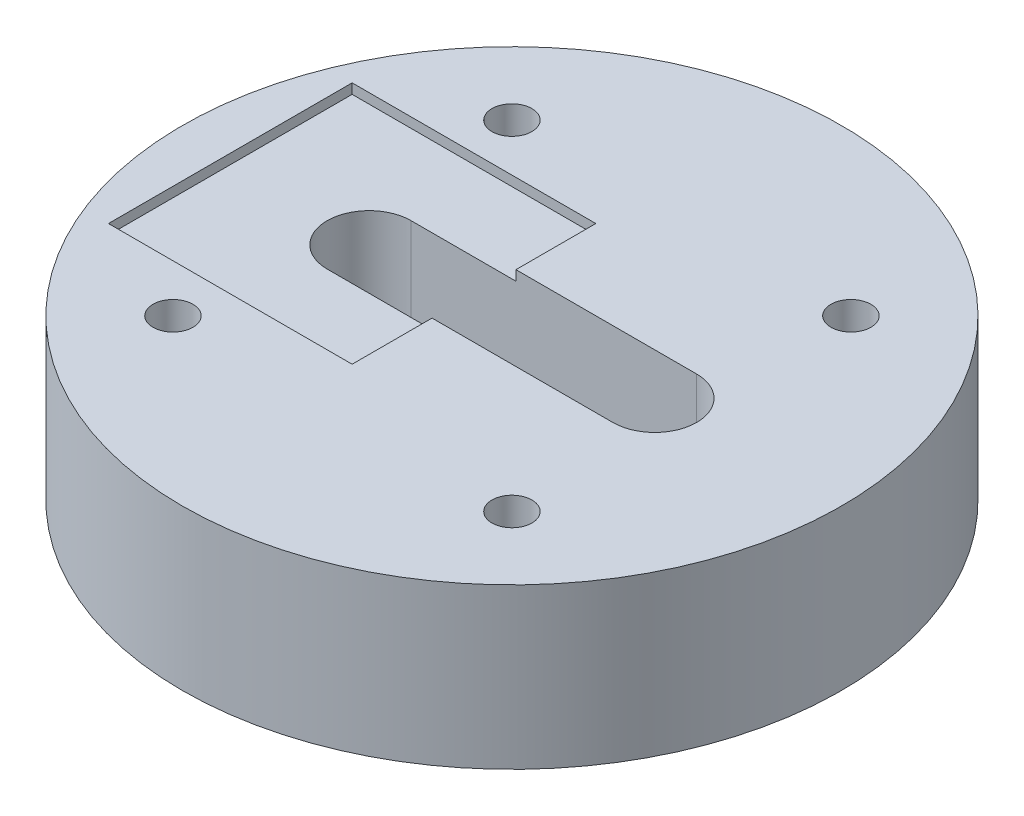
SolidWorks part; units mm, degrees
ref_plane "前视基准面" through (0, 0, 0) normal (0, 0, 1) x (1, 0, 0)
ref_plane "上视基准面" through (0, 0, 0) normal (0, 1, 0) x (1, 0, 0)
ref_plane "右视基准面" through (0, 0, 0) normal (1, 0, 0) x (0, 0, -1)
other "Configuration Table"
sketch "草图1" plane through (0, 0, 0) normal (0, 1, 0) x (1, 0, 0)
  circle A0 centre (0, 0) radius 16.5
  circle A1 centre (0, 0) radius 15.5
  dimension "D1" = 33
  dimension "D2" = 31
extrude "凸台-拉伸1" add sketch "草图1" along normal blind 8 contours A0
extrude "凸台-拉伸2" add sketch "草图1<5>" along normal blind 6 contours A0 | A1
sketch "草图1<5>" plane through (0, 0, 0) normal (0, 1, 0) x (1, 0, 0) same geometry as "草图1"
sketch "草图2" plane through (0, 8, 0) normal (0, 1, 0) x (1, 0, 0)
  line L1 (4.25, 2.1) -> (-4.25, 2.1)
  line L2 (4.25, 2.1) -> (4.25, -2.1)
  line L3 (4.25, -2.1) -> (-4.25, -2.1)
  line L4 (-4.25, 2.1) -> (-4.25, -2.1)
  line L5 (4.25, 2.1) -> (-4.25, -2.1) construction
  line L6 (4.25, -2.1) -> (-4.25, 2.1) construction
  circle A0 centre (4.25, 0) radius 2.1
  circle A1 centre (-4.25, 0) radius 2.1
  dimension "D1" = 4.2
  dimension "D2" = 8.5
extrude "切除-拉伸1" cut sketch "草图2" against normal through all contours L4 A1 | L2 A0 | L1 L4 L3 L2 region at (5.1413, 8, 0) region at (-5.1413, 8, 0)
sketch "草图3" plane through (0, 8, 0) normal (0, 1, 0) x (1, 0, 0)
  line L1 (-7.15, -2.1) -> (7.15, -2.1)
  line L2 (-7.15, -2.1) -> (-7.15, 2.1)
  line L3 (-7.15, 2.1) -> (7.15, 2.1)
  line L4 (7.15, -2.1) -> (7.15, 2.1)
  line L5 (-7.15, -2.1) -> (7.15, 2.1) construction
  line L6 (-7.15, 2.1) -> (7.15, -2.1) construction
  circle A0 centre (-7.15, 0) radius 2.1
  circle A1 centre (7.15, 0) radius 2.1
  point P0 (0, 0)
  dimension "D1" = 4.2
  dimension "D2" = 14.3
extrude "切除-拉伸2" cut sketch "草图3" against normal offset from surface (6 mm away) 2 contours L2 A0 | L4 A1 | L3 L4 L1 L2 region at (-8.0413, 8, 0) region at (8.0413, 8, 0) up to face at (0, 0, 16.5)
sketch "草图4" plane through (0, 2, 0) normal (0, 1, 0) x (1, 0, 0)
  circle A0 centre (-7.7, 0) radius 0.4
  circle A1 centre (7.7, 0) radius 0.4
  dimension "D1" = 0.8
extrude "切除-拉伸3" cut sketch "草图4" against normal blind 2
sketch "草图5" plane through (0, 8, 0) normal (0, 1, 0) x (1, 0, 0)
  line L0 (5.1, 0) -> (0, 0) construction
  line L1 (-1.9, 6.1) -> (-14.1, 6.1)
  line L2 (-1.9, 6.1) -> (-1.9, -6.1)
  line L3 (-1.9, -6.1) -> (-14.1, -6.1)
  line L4 (-14.1, 6.1) -> (-14.1, -6.1)
  line L5 (5.1, 1.6) -> (-1.9, 1.6)
  line L6 (5.1, 1.6) -> (5.1, -1.6)
  line L7 (5.1, -1.6) -> (-1.9, -1.6)
  line L8 (-1.9, 1.6) -> (-1.9, -1.6)
  line L9 (0, 0) -> (-8, 0) construction
  line L10 (-8, 6.1) -> (-8, -6.1) construction
  dimension "D1" = 12.2
  dimension "D2" = 7
  dimension "D3" = 3.2
  dimension "D4" = 8
extrude "切除-拉伸4" cut sketch "草图5" against normal blind 0.5 contours L3 L4 L1 L2 | L7 L8 L5 L6
sketch "草图6" plane through (0, 0, 0) normal (0, -1, 0) x (1, 0, 0)
  line L0 (0, 0) -> (0, 23.2306)
  line L1 (8.4853, 8.4853) -> (0, 0)
  circle A0 centre (8.4853, 8.4853) radius 2
  circle A1 centre (8.4853, 8.4853) radius 1
  dimension "D2" = 4
  dimension "D3" = 2
  dimension "D1" = 45
  dimension "D4" = 12
extrude "切除-拉伸5" cut sketch "草图6" against normal through all contours A1
extrude "切除-拉伸6" cut sketch "草图6<3>" against normal offset from surface (5 mm away) 3 contours A0 up to face at (8.4853, 8, 7.4853)
sketch "草图6<3>" plane through (0, 0, 0) normal (0, -1, 0) x (1, 0, 0) same geometry as "草图6"
pattern_circular "阵列(圆周)1" count 4 over 360 about axis through (0, 8, 0) along (0, -1, 0) of "切除-拉伸5", "切除-拉伸6"
